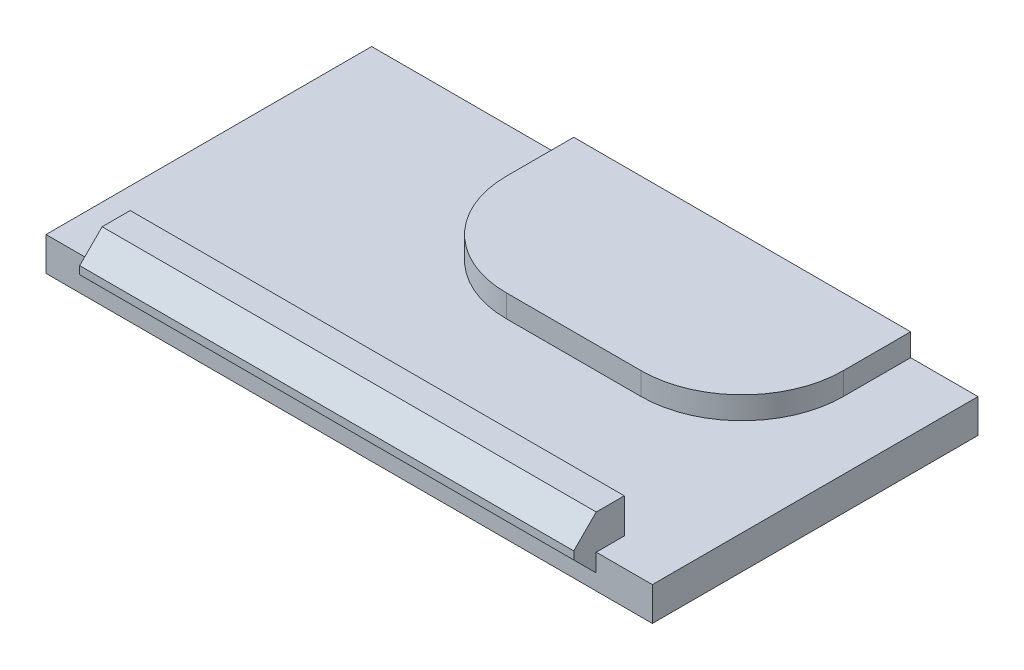
SolidWorks part; units mm, degrees
ref_plane "Front Plane" through (0, 0, 0) normal (0, 0, 1) x (1, 0, 0)
ref_plane "Top Plane" through (0, 0, 0) normal (0, 1, 0) x (1, 0, 0)
ref_plane "Right Plane" through (0, 0, 0) normal (1, 0, 0) x (0, 0, -1)
sketch "Sketch1" plane through (0, 0, 0) normal (0, 1, 0) x (1, 0, 0)
  line L1 (0, 0) -> (68.58, 0)
  line L2 (0, 0) -> (0, 36.83)
  line L3 (0, 36.83) -> (68.58, 36.83)
  line L4 (68.58, 0) -> (68.58, 36.83)
  dimension "D1" = 68.58
  dimension "D2" = 36.83
extrude "Boss-Extrude1" add sketch "Sketch1" along normal blind 3.81
sketch "Sketch3" plane through (0, 0, 0) normal (0, -1, 0) x (1, 0, 0)
  line L0 (34.29, 0) -> (34.29, -21.59) construction
  line L1 (0, 0) -> (68.58, 0) construction
  line L2 (68.58, -36.83) -> (0, -36.83) construction
  line L10 (34.29, -21.59) -> (49.53, -21.59)
  line L11 (57.15, -29.21) -> (57.15, -36.83)
  line L14 (26.67, -29.21) -> (26.67, -36.83)
  line L16 (57.15, -36.83) -> (26.67, -36.83)
  arc A2 (34.29, -21.59) -> (26.67, -29.21) centre (34.29, -29.21) ccw
  arc A3 (57.15, -29.21) -> (49.53, -21.59) centre (49.53, -29.21) ccw
  dimension "D1" = 15.24
  dimension "D3" = 7.62
  dimension "D2" = 15.24
  dimension "D4" = 7.62
  dimension "D5" = 15.24
extrude "Cut-Extrude1" cut sketch "Sketch3" against normal blind 3.81
sketch "Sketch5" plane through (0, 0, 0) normal (0, 0, 1) x (1, 0, 0)
  line L0 (0, 3.81) -> (0, 0) construction
  line L1 (6.35, 1.5875) -> (62.23, 1.5875)
  line L2 (6.35, 1.5875) -> (6.35, 7.9375)
  line L3 (6.35, 7.9375) -> (62.23, 7.9375)
  line L4 (62.23, 1.5875) -> (62.23, 7.9375)
  line L5 (68.58, 3.81) -> (68.58, 0) construction
  line L6 (0, 0) -> (68.58, 0) construction
  dimension "D1" = 6.35
  dimension "D2" = 6.35
  dimension "D3" = 1.5875
  dimension "D4" = 6.35
extrude "Boss-Extrude3" add sketch "Sketch5" along normal blind 2.54
chamfer "Chamfer1" distance 2.7305 angle 45 2 edges at (34.29, 1.5875, 2.54) (34.29, 7.9375, 2.54)
sketch "Sketch6" plane through (0, 0, 0) normal (0, 0, -1) x (-1, 0, 0)
  line L5 (-62.23, 7.747) -> (-6.35, 7.747)
  line L6 (-62.23, 7.747) -> (-62.23, 3.81)
  line L7 (-62.23, 3.81) -> (-6.35, 3.81)
  line L8 (-6.35, 7.747) -> (-6.35, 3.81)
extrude "Boss-Extrude4" add sketch "Sketch6" along normal blind 3.175
sketch "Sketch7" plane through (0, 0, 0) normal (0, -1, 0) x (1, 0, 0)
  line L0 (0, -8.255) -> (68.58, -8.255) construction
  line L1 (0, -36.83) -> (0, 0) construction
  line L2 (68.58, 0) -> (68.58, -36.83) construction
  line L4 (49.53, -21.59) -> (34.29, -21.59) construction
  text T0 "<b>BATTERY</b>" font "Unispace" height 6.35
  dimension "D1" = 13.335
extrude "Cut-Extrude2" cut sketch "Sketch7" against normal blind 0.635
sketch "Sketch8" plane through (0, 3.81, 0) normal (0, 1, 0) x (1, 0, 0)
  line L0 (60.96, 36.83) -> (60.96, 17.78)
  line L1 (68.58, 36.83) -> (57.15, 36.83) construction
  line L2 (34.29, 17.78) -> (60.96, 17.78)
  line L3 (22.86, 29.21) -> (22.86, 36.83)
  line L4 (26.67, 36.83) -> (0, 36.83) construction
  line L5 (26.67, 29.21) -> (26.67, 36.83) construction
  line L6 (57.15, 36.83) -> (57.15, 29.21) construction
  line L11 (49.53, 21.59) -> (34.29, 21.59) construction
  line L12 (60.96, 36.83) -> (22.86, 36.83)
  arc A0 (22.86, 29.21) -> (34.29, 17.78) centre (34.29, 29.21) ccw
  arc A1 (26.67, 29.21) -> (34.29, 21.59) centre (34.29, 29.21) ccw construction
  arc A2 (49.53, 17.78) -> (60.96, 29.21) centre (49.53, 29.21) ccw
  arc A3 (49.53, 21.59) -> (57.15, 29.21) centre (49.53, 29.21) ccw construction
  line M8 (68.58, 36.83) -> (57.15, 36.83)
  line M9 (57.15, 36.83) -> (57.15, 29.21)
  arc M10 (57.15, 29.21) -> (49.53, 21.59) centre (49.53, 29.21) cw
  line M11 (49.53, 21.59) -> (34.29, 21.59)
  arc M12 (34.29, 21.59) -> (26.67, 29.21) centre (34.29, 29.21) cw
  line M13 (26.67, 29.21) -> (26.67, 36.83)
  line M14 (26.67, 36.83) -> (0, 36.83)
  dimension "D1" = 3.81
  dimension "D2" = 3.81
  dimension "D3" = 3.81
extrude "Boss-Extrude5" add sketch "Sketch8" along normal blind 2.54 contours L2 A2 L0 L3 A0 M8 M9 M10 M11 M12 M13 M14 | L12 M9 M13 M12 M11 M10 region at (60.534, 3.81, -33.02) region at (41.91, 3.81, -29.5455)
sketch "Sketch9" plane through (0, 3.81, 0) normal (0, -1, 0) x (1, 0, 0)
  line L0 (26.67, -36.83) -> (57.15, -36.83)
  line L1 (57.15, -36.83) -> (57.15, -29.21)
  line L2 (49.53, -21.59) -> (34.29, -21.59)
  line L3 (26.67, -36.83) -> (26.67, -29.21)
  arc A0 (26.67, -29.21) -> (34.29, -21.59) centre (34.29, -29.21) cw
  arc A1 (57.15, -29.21) -> (49.53, -21.59) centre (49.53, -29.21) ccw
  arc A2 (34.29, -21.59) -> (26.67, -29.21) centre (34.29, -29.21) ccw construction
  arc A3 (57.15, -29.21) -> (49.53, -21.59) centre (49.53, -29.21) ccw construction
extrude "Cut-Extrude3" cut sketch "Sketch9" against normal blind 0.635
